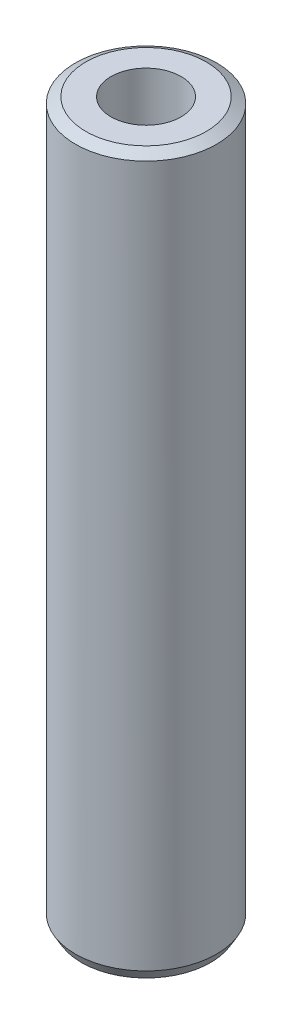
SolidWorks part; units mm, degrees
ref_plane "Front Plane" through (0, 0, 0) normal (0, 0, 1) x (1, 0, 0)
ref_plane "Top Plane" through (0, 0, 0) normal (0, 1, 0) x (1, 0, 0)
ref_plane "Right Plane" through (0, 0, 0) normal (1, 0, 0) x (0, 0, -1)
sketch "Sketch1" plane through (0, 0, 0) normal (0, 1, 0) x (1, 0, 0)
  circle A0 centre (0, 0) radius 35
  dimension "SHAFT_OD" = 70
extrude "Boss-Extrude1" add sketch "Sketch1" along normal blind 355.8967
sketch "Sketch2" plane through (0, 0, 0) normal (0, 1, 0) x (1, 0, 0)
  circle A0 centre (0, 0) radius 17.3707
  dimension "BORE_D" = 34.7415
extrude "Cut-Extrude1" cut sketch "Sketch2" along normal through all
chamfer "Chamfer1" distance 2.952 angle 60 2 edges at (0, 355.8967, 35) (0, 0, 35) first distance on face at (0, 355.8967, 35) first distance on face at (0, 0, 17.3707)
